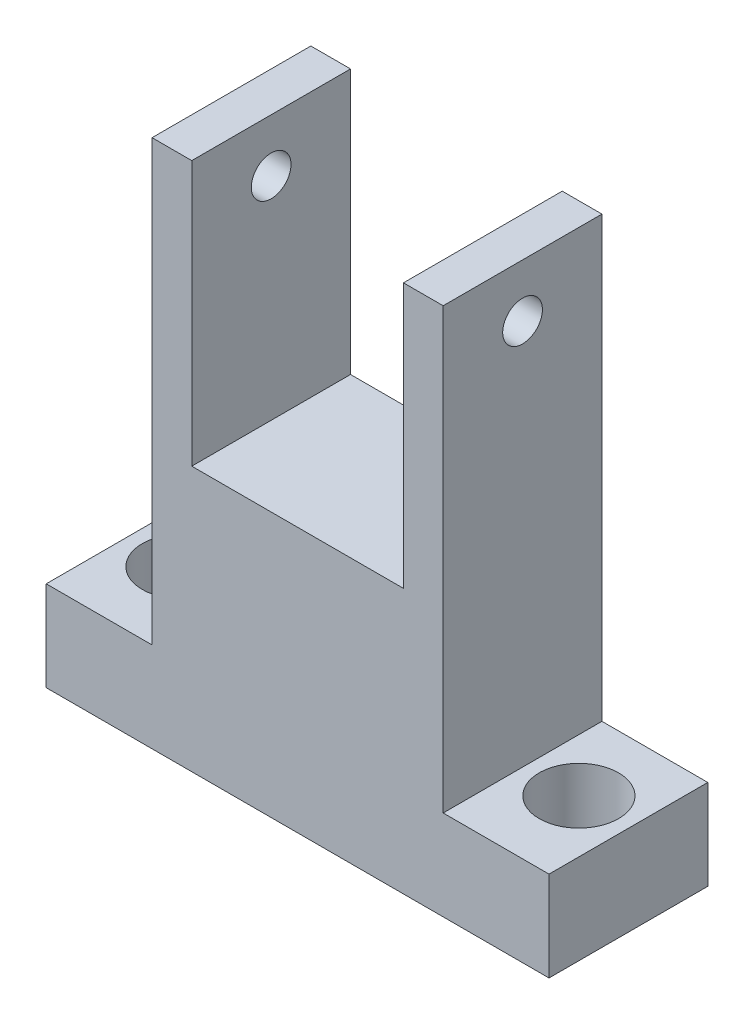
SolidWorks part; units mm, degrees
ref_plane "Plan de face" through (0, 0, 0) normal (0, 0, 1) x (1, 0, 0)
ref_plane "Plan de dessus" through (0, 0, 0) normal (0, 1, 0) x (1, 0, 0)
ref_plane "Plan de droite" through (0, 0, 0) normal (1, 0, 0) x (0, 0, -1)
sketch "Sketch1" plane through (0, 0, 0) normal (0, 1, 0) x (1, 0, 0)
  line L0 (0, 0) -> (0, 15.1381) construction
  line L1 (-5.5, 3) -> (5.5, 3)
  line L2 (-5.5, 3) -> (-5.5, -3)
  line L3 (-5.5, -3) -> (5.5, -3)
  line L4 (5.5, 3) -> (5.5, -3)
  line L5 (-9.5, 3) -> (9.5, 3)
  line L6 (-9.5, 3) -> (-9.5, -3)
  line L7 (-9.5, -3) -> (9.5, -3)
  line L8 (9.5, 3) -> (9.5, -3)
  line L10 (-4, 3) -> (4, 3)
  line L11 (-4, 3) -> (-4, -3)
  line L12 (-4, -3) -> (4, -3)
  line L13 (4, 3) -> (4, -3)
  circle A0 centre (-7.5, 0.129) radius 1.5
  circle A1 centre (7.5, 0.129) radius 1.5
  point P4 (0, 3)
  point P6 (-5.5, 0)
  point P11 (0, 3)
  point P12 (-9.5, 0)
  point P23 (0, 3)
  dimension "D3" = 3
  dimension "D1" = 11
  dimension "D2" = 6
  dimension "D4" = 7.5
  dimension "D5" = 2
  dimension "D6" = 8
extrude "Boss-Extrude1" add sketch "Sketch1" along normal blind 3.4 contours L6 L7 L2 L5 A0 | L11 L1 L2 L3 | L7 L0 L5 L11 | L0 L12 L13 L10 | L1 L13 L3 L4 | L8 L5 L4 L7 A1 region at (-4.75, 0, 0) region at (-5.5721, 0, 0) region at (-2, 0, -2.9) region at (4.75, 0, 0) region at (7.5, 0, -2.9279)
extrude "Boss-Extrude2" add sketch "Sketch1<4>" along normal blind 20 contours L11 L1 L2 L3 | L1 L13 L3 L4 region at (-4.75, 0, 0) region at (4.75, 0, 0)
sketch "Sketch1<4>" plane through (0, 0, 0) normal (0, 1, 0) x (1, 0, 0) same geometry as "Sketch1"
sketch "Sketch2" plane through (5.5, 0, 0) normal (1, 0, 0) x (0, 0, -1)
  line L0 (3, 20) -> (-3, 20) construction
  circle A0 centre (0, 18) radius 0.75
  dimension "D1" = 1.5
  dimension "D2" = 2
extrude "Cut-Extrude1" cut sketch "Sketch2" against normal through all both and the other way through all
extrude "Boss-Extrude3" add sketch "Sketch1<5>" along normal blind 10 contours L7 L0 L5 L11 | L0 L12 L13 L10 region at (-2, 0, -2.9)
sketch "Sketch1<5>" plane through (0, 0, 0) normal (0, 1, 0) x (1, 0, 0) same geometry as "Sketch1"
